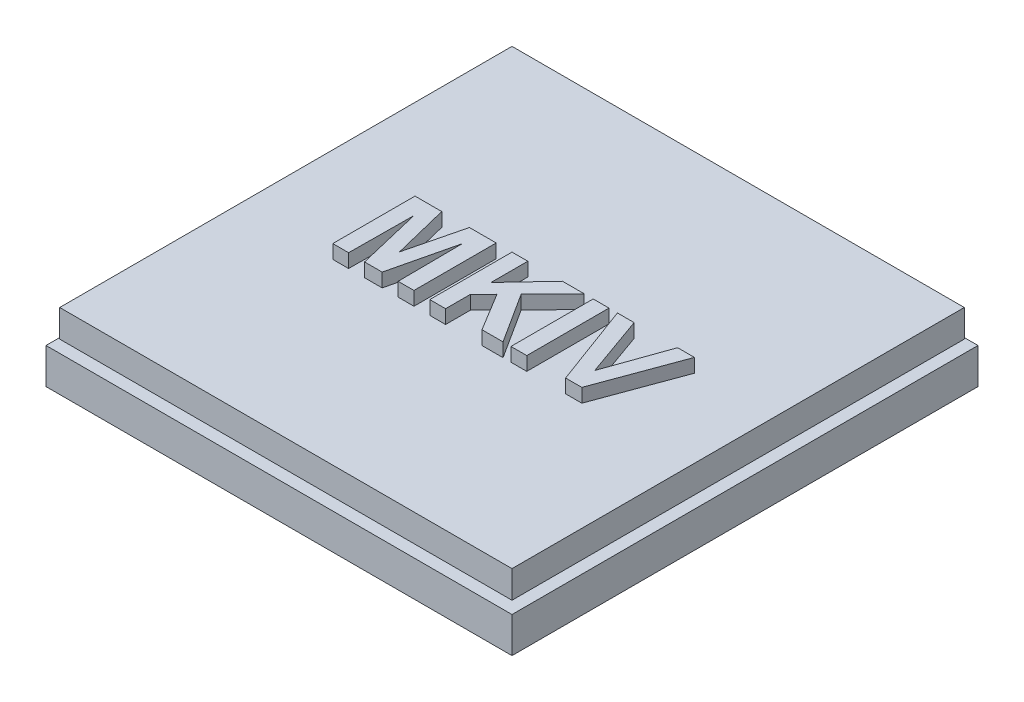
SolidWorks part; units mm, degrees
ref_plane "Спереди" through (0, 0, 0) normal (0, 0, 1) x (1, 0, 0)
ref_plane "Сверху" through (0, 0, 0) normal (0, 1, 0) x (1, 0, 0)
ref_plane "Справа" through (0, 0, 0) normal (1, 0, 0) x (0, 0, -1)
sketch "Sketch1" plane through (0, 0, 0) normal (0, 1, 0) x (1, 0, 0)
  line L1 (14.85, -14.85) -> (-14.85, -14.85)
  line L2 (14.85, -14.85) -> (14.85, 14.85)
  line L3 (14.85, 14.85) -> (-14.85, 14.85)
  line L4 (-14.85, -14.85) -> (-14.85, 14.85)
  line L5 (14.85, -14.85) -> (-14.85, 14.85) construction
  line L6 (14.85, 14.85) -> (-14.85, -14.85) construction
  point P0 (0, 0)
  dimension "D1" = 29.7
extrude "Boss-Extrude1" add sketch "Sketch1" along normal blind 3
sketch "Sketch2" plane through (0, 3, 0) normal (0, 1, 0) x (1, 0, 0)
  line L1 (16.5, -16.5) -> (-16.5, -16.5)
  line L2 (16.5, -16.5) -> (16.5, 16.5)
  line L3 (16.5, 16.5) -> (-16.5, 16.5)
  line L4 (-16.5, -16.5) -> (-16.5, 16.5)
  line L5 (16.5, -16.5) -> (-16.5, 16.5) construction
  line L6 (16.5, 16.5) -> (-16.5, -16.5) construction
  point P0 (0, 0)
  dimension "D1" = 33
extrude "Boss-Extrude2" add sketch "Sketch2" along normal blind 2
sketch "Sketch3" plane through (0, 5, 0) normal (0, 1, 0) x (1, 0, 0)
  line L0 (-16.5, -3.5) -> (16.5, -3.5) construction
  line L1 (-16.5, 16.5) -> (-16.5, -16.5) construction
  line L2 (16.5, -16.5) -> (16.5, 16.5) construction
  line L3 (-16.5, -16.5) -> (16.5, -16.5) construction
  text T0 "<b>MKIV</b>" font "Arial" height 6
  dimension "D1" = 13
extrude "Boss-Extrude3" add sketch "Sketch3" along normal blind 1
sketch "Sketch5" plane through (0, 0, 0) normal (0, -1, 0) x (1, 0, 0)
  line L1 (-17, 17) -> (17, 17)
  line L2 (-17, 17) -> (-17, -17)
  line L3 (-17, -17) -> (17, -17)
  line L4 (17, 17) -> (17, -17)
  line L5 (-17, 17) -> (17, -17) construction
  line L6 (-17, -17) -> (17, 17) construction
  line L7 (-15.5, 15.5) -> (15.5, 15.5)
  line L8 (-15.5, 15.5) -> (-15.5, -15.5)
  line L9 (-15.5, -15.5) -> (15.5, -15.5)
  line L10 (15.5, 15.5) -> (15.5, -15.5)
  line L11 (-15.5, 15.5) -> (15.5, -15.5) construction
  line L12 (-15.5, -15.5) -> (15.5, 15.5) construction
  point P0 (0, 0)
  point P6 (0, 0)
  dimension "D1" = 31
  dimension "D2" = 34
extrude "Boss-Extrude4" add sketch "Sketch5" against normal offset from surface (2.6 mm away) 0.4 separate body up to face at (0, 3, 0)
chamfer "Chamfer1" distance 0.5 angle 60 4 edges at (14.85, 0, 0) (0, 0, 14.85) (-14.85, 0, 0) (0, 0, -14.85) first distance on face at (0, 0, 0)
